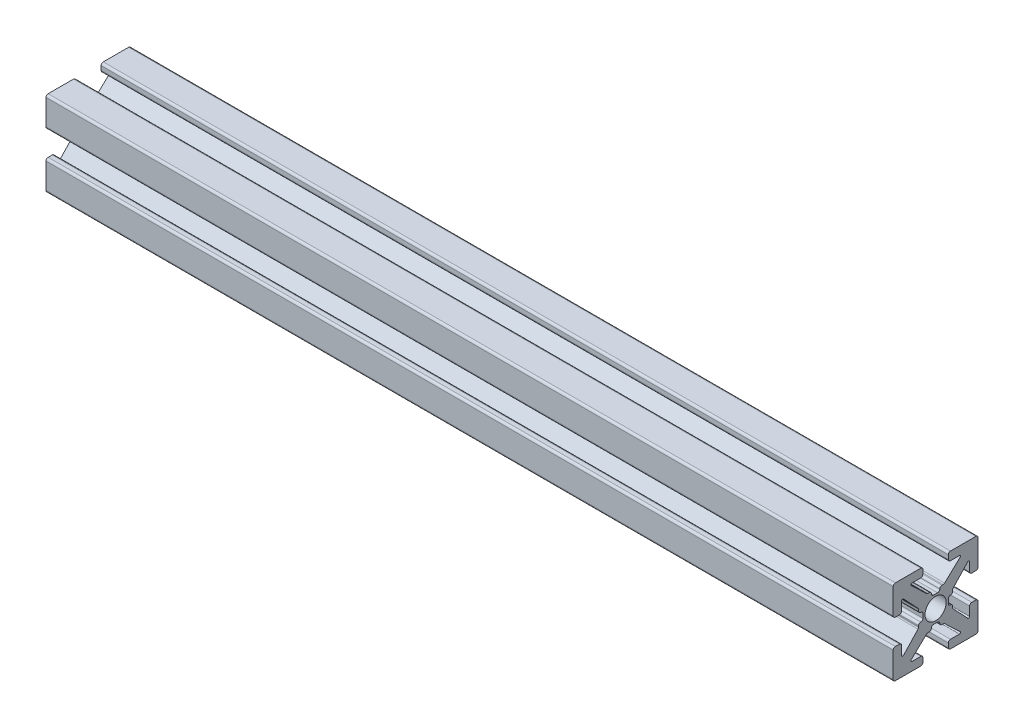
SolidWorks part; units mm, degrees
material "Acciaio in lega fuso"
ref_plane "Front Plane" through (0, 0, 0) normal (0, 0, 1) x (1, 0, 0)
ref_plane "Top Plane" through (0, 0, 0) normal (0, 1, 0) x (1, 0, 0)
ref_plane "Right Plane" through (0, 0, 0) normal (1, 0, 0) x (0, 0, -1)
sketch "Sketch1" plane through (0, 0, 0) normal (1, 0, 0) x (0, 0, -1)
  line L0 (0, 0) -> (0, 1.4986) construction
  line L1 (-0.2413, 1.4986) -> (0.2413, 1.4986)
  line L2 (5.0038, 1.7526) -> (5.0038, 4.7498)
  line L3 (0.7493, 2.0066) -> (0.8899, 2.0066)
  line L4 (1.0639, 2.0756) -> (2.8908, 3.7937)
  line L5 (2.8038, 4.0132) -> (1.7526, 4.0132)
  line L6 (1.4986, 4.2672) -> (1.4986, 4.7498)
  line L7 (1.7526, 5.0038) -> (4.7498, 5.0038)
  line L8 (5.0038, 5.0038) -> (0, 0) construction
  line L9 (0, 0) -> (8.6271, 0) construction
  line L10 (0, 0) -> (0, 5.0038) construction
  line L11 (4.2672, 1.4986) -> (4.7498, 1.4986)
  line L12 (4.0132, 2.8038) -> (4.0132, 1.7526)
  line L13 (2.0756, 1.0639) -> (3.7937, 2.8908)
  line L14 (2.0066, 0.7493) -> (2.0066, 0.8899)
  line L15 (1.4986, -0.2413) -> (1.4986, 0.2413)
  line L16 (0, 0) -> (1.4986, 0) construction
  line L17 (-0.2413, -1.4986) -> (0.2413, -1.4986)
  line L18 (0.7493, -2.0066) -> (0.8899, -2.0066)
  line L19 (1.0639, -2.0756) -> (2.8908, -3.7937)
  line L20 (2.8038, -4.0132) -> (1.7526, -4.0132)
  line L21 (1.4986, -4.2672) -> (1.4986, -4.7498)
  line L22 (1.7526, -5.0038) -> (4.7498, -5.0038)
  line L23 (5.0038, -1.7526) -> (5.0038, -4.7498)
  line L24 (4.2672, -1.4986) -> (4.7498, -1.4986)
  line L25 (4.0132, -2.8038) -> (4.0132, -1.7526)
  line L26 (2.0756, -1.0639) -> (3.7937, -2.8908)
  line L27 (2.0066, -0.7493) -> (2.0066, -0.8899)
  line L28 (-0.7493, 2.0066) -> (-0.8899, 2.0066)
  line L29 (-1.0639, 2.0756) -> (-2.8908, 3.7937)
  line L30 (-2.8038, 4.0132) -> (-1.7526, 4.0132)
  line L31 (-1.4986, 4.2672) -> (-1.4986, 4.7498)
  line L32 (-1.7526, 5.0038) -> (-4.7498, 5.0038)
  line L33 (-5.0038, 1.7526) -> (-5.0038, 4.7498)
  line L34 (-4.2672, 1.4986) -> (-4.7498, 1.4986)
  line L35 (-4.0132, 2.8038) -> (-4.0132, 1.7526)
  line L36 (-2.0756, 1.0639) -> (-3.7937, 2.8908)
  line L37 (-2.0066, 0.7493) -> (-2.0066, 0.8899)
  line L38 (-1.4986, -0.2413) -> (-1.4986, 0.2413)
  line L39 (-2.0066, -0.7493) -> (-2.0066, -0.8899)
  line L40 (-2.0756, -1.0639) -> (-3.7937, -2.8908)
  line L41 (-4.0132, -2.8038) -> (-4.0132, -1.7526)
  line L42 (-4.2672, -1.4986) -> (-4.7498, -1.4986)
  line L43 (-5.0038, -1.7526) -> (-5.0038, -4.7498)
  line L44 (-1.7526, -5.0038) -> (-4.7498, -5.0038)
  line L45 (-1.4986, -4.2672) -> (-1.4986, -4.7498)
  line L46 (-2.8038, -4.0132) -> (-1.7526, -4.0132)
  line L47 (-1.0639, -2.0756) -> (-2.8908, -3.7937)
  line L48 (-0.7493, -2.0066) -> (-0.8899, -2.0066)
  arc A0 (2.8908, 3.7937) -> (2.8038, 4.0132) centre (2.8038, 3.8862) ccw
  arc A1 (0.4953, 1.7526) -> (0.7493, 2.0066) centre (0.7493, 1.7526) cw
  arc A2 (0.8899, 2.0066) -> (1.0639, 2.0756) centre (0.8899, 2.2606) ccw
  arc A3 (1.7526, 4.0132) -> (1.4986, 4.2672) centre (1.7526, 4.2672) cw
  arc A4 (1.4986, 4.7498) -> (1.7526, 5.0038) centre (1.7526, 4.7498) cw
  arc A5 (0.2413, 1.4986) -> (0.4953, 1.7526) centre (0.2413, 1.7526) ccw
  arc A6 (4.7498, 1.4986) -> (5.0038, 1.7526) centre (4.7498, 1.7526) ccw
  arc A7 (4.0132, 1.7526) -> (4.2672, 1.4986) centre (4.2672, 1.7526) ccw
  arc A8 (3.7937, 2.8908) -> (4.0132, 2.8038) centre (3.8862, 2.8038) cw
  arc A9 (2.0066, 0.8899) -> (2.0756, 1.0639) centre (2.2606, 0.8899) cw
  arc A10 (1.7526, 0.4953) -> (2.0066, 0.7493) centre (1.7526, 0.7493) ccw
  arc A11 (1.4986, 0.2413) -> (1.7526, 0.4953) centre (1.7526, 0.2413) cw
  arc A12 (0.2413, -1.4986) -> (0.4953, -1.7526) centre (0.2413, -1.7526) cw
  arc A13 (0.4953, -1.7526) -> (0.7493, -2.0066) centre (0.7493, -1.7526) ccw
  arc A14 (0.8899, -2.0066) -> (1.0639, -2.0756) centre (0.8899, -2.2606) cw
  arc A15 (2.8908, -3.7937) -> (2.8038, -4.0132) centre (2.8038, -3.8862) cw
  arc A16 (1.7526, -4.0132) -> (1.4986, -4.2672) centre (1.7526, -4.2672) ccw
  arc A17 (1.4986, -4.7498) -> (1.7526, -5.0038) centre (1.7526, -4.7498) ccw
  arc A18 (4.7498, -1.4986) -> (5.0038, -1.7526) centre (4.7498, -1.7526) cw
  arc A19 (4.0132, -1.7526) -> (4.2672, -1.4986) centre (4.2672, -1.7526) cw
  arc A20 (3.7937, -2.8908) -> (4.0132, -2.8038) centre (3.8862, -2.8038) ccw
  arc A21 (2.0066, -0.8899) -> (2.0756, -1.0639) centre (2.2606, -0.8899) ccw
  arc A22 (1.7526, -0.4953) -> (2.0066, -0.7493) centre (1.7526, -0.7493) cw
  arc A23 (1.4986, -0.2413) -> (1.7526, -0.4953) centre (1.7526, -0.2413) ccw
  arc A24 (-0.2413, 1.4986) -> (-0.4953, 1.7526) centre (-0.2413, 1.7526) cw
  arc A25 (-0.4953, 1.7526) -> (-0.7493, 2.0066) centre (-0.7493, 1.7526) ccw
  arc A26 (-0.8899, 2.0066) -> (-1.0639, 2.0756) centre (-0.8899, 2.2606) cw
  arc A27 (-2.8908, 3.7937) -> (-2.8038, 4.0132) centre (-2.8038, 3.8862) cw
  arc A28 (-1.7526, 4.0132) -> (-1.4986, 4.2672) centre (-1.7526, 4.2672) ccw
  arc A29 (-1.4986, 4.7498) -> (-1.7526, 5.0038) centre (-1.7526, 4.7498) ccw
  arc A30 (-4.7498, 1.4986) -> (-5.0038, 1.7526) centre (-4.7498, 1.7526) cw
  arc A31 (-4.0132, 1.7526) -> (-4.2672, 1.4986) centre (-4.2672, 1.7526) cw
  arc A32 (-3.7937, 2.8908) -> (-4.0132, 2.8038) centre (-3.8862, 2.8038) ccw
  arc A33 (-2.0066, 0.8899) -> (-2.0756, 1.0639) centre (-2.2606, 0.8899) ccw
  arc A34 (-1.7526, 0.4953) -> (-2.0066, 0.7493) centre (-1.7526, 0.7493) cw
  arc A35 (-1.4986, 0.2413) -> (-1.7526, 0.4953) centre (-1.7526, 0.2413) ccw
  arc A36 (-1.4986, -0.2413) -> (-1.7526, -0.4953) centre (-1.7526, -0.2413) cw
  arc A37 (-1.7526, -0.4953) -> (-2.0066, -0.7493) centre (-1.7526, -0.7493) ccw
  arc A38 (-2.0066, -0.8899) -> (-2.0756, -1.0639) centre (-2.2606, -0.8899) cw
  arc A39 (-3.7937, -2.8908) -> (-4.0132, -2.8038) centre (-3.8862, -2.8038) cw
  arc A40 (-4.0132, -1.7526) -> (-4.2672, -1.4986) centre (-4.2672, -1.7526) ccw
  arc A41 (-4.7498, -1.4986) -> (-5.0038, -1.7526) centre (-4.7498, -1.7526) ccw
  arc A42 (-1.4986, -4.7498) -> (-1.7526, -5.0038) centre (-1.7526, -4.7498) cw
  arc A43 (-1.7526, -4.0132) -> (-1.4986, -4.2672) centre (-1.7526, -4.2672) cw
  arc A44 (-2.8908, -3.7937) -> (-2.8038, -4.0132) centre (-2.8038, -3.8862) ccw
  arc A45 (-0.8899, -2.0066) -> (-1.0639, -2.0756) centre (-0.8899, -2.2606) ccw
  arc A46 (-0.4953, -1.7526) -> (-0.7493, -2.0066) centre (-0.7493, -1.7526) cw
  arc A47 (-0.2413, -1.4986) -> (-0.4953, -1.7526) centre (-0.2413, -1.7526) ccw
  arc A48 (-4.7498, 5.0038) -> (-5.0038, 4.7498) centre (-4.7498, 4.7498) ccw
  arc A49 (-5.0038, -4.7498) -> (-4.7498, -5.0038) centre (-4.7498, -4.7498) ccw
  arc A50 (4.7498, -5.0038) -> (5.0038, -4.7498) centre (4.7498, -4.7498) ccw
  arc A51 (4.7498, 5.0038) -> (5.0038, 4.7498) centre (4.7498, 4.7498) cw
  point P14 (3.1242, 4.0132)
  point P19 (0.9906, 2.0066)
  point P150 (0, -1.4986)
  point P152 (-5.0038, 5.0038)
  point P155 (-5.0038, -5.0038)
  point P158 (5.0038, -5.0038)
  dimension "D10" = 0.127
  dimension "D11" = 0.254
  dimension "D2" = 0.254
  dimension "D1" = 10.0076
  dimension "D3" = 2.9972
  dimension "D4" = 0.508
  dimension "D5" = 2.9972
  dimension "D6" = 0.9906
  dimension "D7" = 1.6256
  dimension "D8" = 1.9812
  dimension "D9" = 0.9906
extrude "Estrusione-Estrusione1" add sketch "Sketch1" along normal blind 100 contours L36 A32 L35 A31 L34 A30 L33 A48 L32 A29 L31 A28 L30 A27 L29 A26 L28 A25 A24 L1 A5 A1 L3 A2 L4 A0 L5 A3 L6 A4 L7 A51 L2 A6 L11 A7 L12 A8 L13 A9 L14 A10 A11 L15 A23 A22 L27 A21 L26 A20 L25 A19 L24 A18 L23 A50 L22 A17 L21 A16 L20 A15 L19 A14 L18 A13 A12 L17 A47 A46 L48 A45 L47 A44 L46 A43 L45 A42 L44 A49 L43 A41 L42 A40 L41 A39 L40 A38 L39 A37 A36 L38 A35 A34 L37 A33
hole_wizard "Foro filettato M3x0.5-1" positions "Schizzo2" profile "Schizzo1" tap size "M3x0.5" standard "Ansi Metric" end condition through all
sketch "Schizzo2" plane through (0, 0, 0) normal (-1, 0, 0) x (0, 0, 1)
  point P0 (0, 0)
sketch "Schizzo1" plane through (0, 0, 0) normal (0, 1, 0) x (0, 0, 1)
  line L0 (0, 0) -> (0, 100)
  line L1 (0, 100) -> (1.25, 100)
  line L2 (1.25, 100) -> (1.25, 0)
  line L5 (1.25, 0) -> (0, 0)
  line L11 (0, -6.35) -> (0, 107.95) construction
  dimension "Thread Major Dia." = 2.5
  dimension "Thru Tap Drill Depth" = 100
